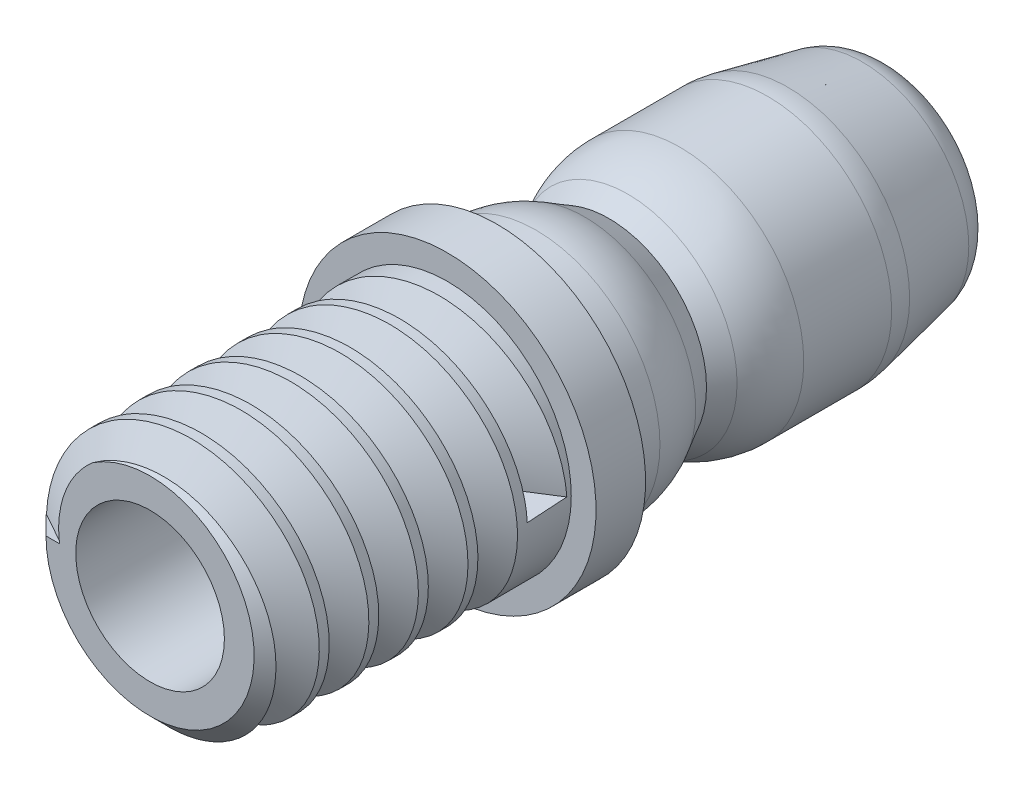
SolidWorks part; units mm, degrees
ref_plane "Front Plane" through (0, 0, 0) normal (0, 0, 1) x (1, 0, 0)
ref_plane "Top Plane" through (0, 0, 0) normal (0, 1, 0) x (1, 0, 0)
ref_plane "Right Plane" through (0, 0, 0) normal (1, 0, 0) x (0, 0, -1)
sketch "Sketch1" plane through (0, 0, 0) normal (0, 0, 1) x (1, 0, 0)
  circle A0 centre (0, 0) radius 0.625
  dimension "D1" = 1.25
extrude "Boss-Extrude1" add sketch "Sketch1" along normal blind 1.5
sketch "Sketch2" plane through (0, 0, 0) normal (0, 0, -1) x (-1, 0, 0)
  circle A0 centre (0, 0) radius 0.75
  dimension "D1" = 1.5
extrude "Boss-Extrude2" add sketch "Sketch2" along normal blind 0.25
chamfer "Chamfer1" distance 0.1 angle 45 1 edges at (0.625, 0, 1.5)
sketch "Sketch3" plane through (0, 0, 1.5) normal (0, 0, 1) x (1, 0, 0)
  circle A0 centre (0, 0) radius 0.625 construction
  circle A1 centre (0, 0) radius 0.625
curve "Helix/Spiral1" pitch 0.25 height 1.375 radius 0.625 centre (0, 0, 1.5) axis (0, 0, -1) start towards (-1, 0, 0)
ref_plane "Plane1" through (-0.625, 0, 1.5) normal (0, 0.998, -0.0635) x (1, 0, 0)
sketch "Sketch4" plane through (-0.625, 0, 1.5) normal (0, 0.998, -0.0635) x (1, 0, 0)
  line L1 (0.173, 0.0027) -> (-0.0175, 0.1127)
  line L2 (-0.0175, 0.1127) -> (-0.0175, -0.1073)
  line L3 (-0.0175, -0.1073) -> (0.173, 0.0027)
  circle A0 centre (0.046, 0.0027) radius 0.0635 construction
  dimension "D1" = 0.22
sweep "Cut-Sweep1" cut profiles "Sketch4" path "Helix/Spiral1"
sketch "Sketch5" plane through (0, 0, -0.25) normal (0, 0, -1) x (-1, 0, 0)
  circle A0 centre (0, 0) radius 0.375
  circle A1 centre (0, 0) radius 0.625
  dimension "D1" = 0.75
  dimension "D2" = 1.25
extrude "Boss-Extrude3" add sketch "Sketch5" along normal blind 2
sketch "Sketch6" plane through (0, 0, 0) normal (0, 1, 0) x (1, 0, 0)
  line L0 (0, 0) -> (0, 2.2884) construction
  line L1 (-0.3947, 2.7848) -> (-0.7232, 1.1907)
  line L2 (-0.7232, 1.1907) -> (-0.492, 0.8152)
  line L3 (-0.492, 0.8152) -> (0.8641, 0.8152) construction
  line L4 (-0.625, 0.5778) -> (-0.492, 0.8152)
  line L6 (-0.3947, 2.7848) -> (-0.8499, 2.7848)
  line L7 (-0.625, 0.5778) -> (-0.625, 0.25)
  line L8 (-0.8499, 2.7848) -> (-0.8499, 0.25)
  line L9 (-0.8499, 0.25) -> (-0.625, 0.25)
  point P11 (-0.492, 0.8152)
revolve "Cut-Revolve1" cut sketch "Sketch6" angle 360 about L0
fillet "Fillet1" radius 0.5 3 edges at (0.625, 0, -0.5778) (-0.625, 0, -1.0312) (0.625, 0, -1.6674)
fillet "Fillet2" radius 0.2 1 edges at (-0.5049, 0, -2.25)
sketch "Sketch7" plane through (0, 0, -0.25) normal (0, 0, -1) x (-1, 0, 0)
  circle A0 centre (0, 0) radius 0.375 construction
  circle A1 centre (0, 0) radius 0.375
extrude "Cut-Extrude1" cut sketch "Sketch7" against normal blind 2
